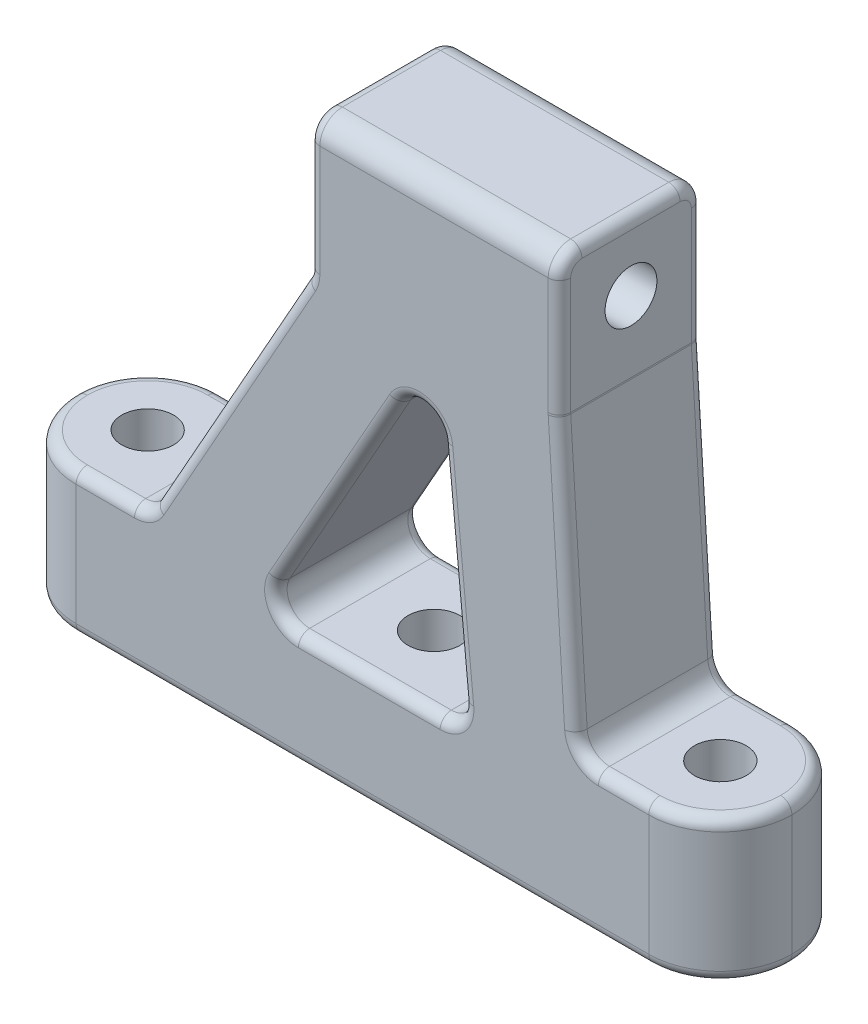
SolidWorks part; units mm, degrees
ref_plane "Front Plane" through (0, 0, 0) normal (0, 0, 1) x (1, 0, 0)
ref_plane "Top Plane" through (0, 0, 0) normal (0, 1, 0) x (1, 0, 0)
ref_plane "Right Plane" through (0, 0, 0) normal (1, 0, 0) x (0, 0, -1)
sketch "Sketch1" plane through (0, 0, 0) normal (0, 0, 1) x (1, 0, 0)
  line L0 (31.75, 0) -> (-31.75, 0)
  line L1 (-31.75, 0) -> (-31.75, 12.7)
  line L2 (-31.75, 12.7) -> (-19.05, 12.7)
  line L3 (-19.05, 12.7) -> (-4.7752, 38.1)
  line L5 (17.4752, 38.1) -> (19.05, 12.7)
  line L6 (19.05, 12.7) -> (31.75, 12.7)
  line L7 (31.75, 12.7) -> (31.75, 0)
  line L8 (-4.7752, 38.1) -> (17.4752, 38.1)
  line L9 (-9.0964, 10) -> (6.4012, 37.5758)
  line L10 (-4.7752, 38.1) -> (17.4752, 38.1)
  line L11 (-4.7752, 38.1) -> (-4.7752, 50.4952)
  line L12 (-4.7752, 50.4952) -> (17.4752, 50.4952)
  line L13 (17.4752, 38.1) -> (17.4752, 50.4952)
  line L14 (6.4012, 37.5758) -> (9.0964, 10)
  line L15 (9.0964, 10) -> (-9.0964, 10)
  line L16 (25.4, 12.7) -> (25.4, 0) construction
  point P4 (0, 0)
  point P14 (6.35, 38.1)
  point P15 (6.35, 50.4952)
  point P17 (0, 10)
  dimension "D1" = 63.5
  dimension "D2" = 12.7
  dimension "D3" = 38.1
  dimension "D4" = 22.2504
  dimension "D5" = 12.3952
  dimension "D6" = 38.1
  dimension "D7" = 10
  dimension "D8" = 10
  dimension "D9" = 19.05
extrude "Boss-Extrude1" add sketch "Sketch1" along normal blind 12.7 contours L16 L6 L5 L8 L3 L2 L1 L0 L14 L15 L9 | L6 L16 L0 L7 | L8 L13 L12 L11 region at (28.575, 6.35, 0) region at (-3.175, 0.6869, 0) region at (6.35, 44.2976, 0)
sketch "Sketch2" plane through (0, 12.7, 0) normal (0, 1, 0) x (1, 0, 0)
  line L0 (-31.75, 0) -> (-19.05, 0) construction
  line L1 (-31.75, -12.7) -> (-31.75, 0) construction
  line L2 (31.75, -12.7) -> (31.75, 0) construction
  circle A0 centre (-25.4, -6.35) radius 2.3
  circle A1 centre (25.4, -6.35) radius 2.3
  circle A2 centre (0, -6.35) radius 2.3
  point P8 (0, 0)
  point P13 (0, 0)
  dimension "D4" = 4.6
  dimension "D1" = 6.35
  dimension "D2" = 6.35
  dimension "D3" = 6.35
extrude "Cut-Extrude1" cut sketch "Sketch2" against normal up to next
sketch "Sketch3" plane through (-4.7752, 0, 0) normal (-1, 0, 0) x (0, 0, 1)
  line L0 (12.7, 38.1) -> (0, 38.1) construction
  line L1 (0, 38.1) -> (0, 50.4952) construction
  circle A0 centre (6.35, 44.45) radius 2.3
  dimension "D1" = 4.6
  dimension "D2" = 6.35
  dimension "D3" = 6.35
extrude "Cut-Extrude2" cut sketch "Sketch3" against normal up to next
fillet "Fillet1" radius 6.35 4 edges at (31.75, 6.35, 0) (31.75, 6.35, 12.7) (-31.75, 6.35, 0) (-31.75, 6.35, 12.7)
fillet "Fillet2" radius 2 9 edges at (6.35, 50.4952, 0) (6.35, 50.4952, 12.7) (9.0964, 10, 6.35) (-9.0964, 10, 6.35) (19.05, 12.7, 6.35) (-19.05, 12.7, 6.35) (-4.7752, 38.1, 6.35) (6.4012, 37.5758, 6.35) (17.4752, 38.1, 6.35)
fillet "Fillet3" radius 1 48 edges at (-7.4044, 10.99, 0) (0.6066, 10, 0) (8.3728, 10.6563, 0) (7.9508, 21.7207, 0) (5.4409, 33.0096, 0) (29.8901, 0, 1.8599) (0, 0, 0) (-29.8901, 0, 1.8599) (-29.8901, 0, 10.8401) (0, 0, 12.7) (-4.8404, 38.1171, 12.7) (-11.7542, 25.6819, 12.7) (-19.2102, 12.9738, 12.7) (-22.8101, 12.7, 12.7) (-29.8901, 12.7, 10.8401) (-29.8901, 12.7, 1.8599) (-22.8101, 12.7, 0) (-19.2102, 12.9738, 0) (-11.7542, 25.6819, 0) (-4.8404, 38.1171, 0) (-4.7752, 43.5593, 0) (-4.7752, 49.9094, 0.5858) (-4.7752, 50.4952, 6.35) (-4.7752, 49.9094, 12.1142) (5.4409, 33.0096, 12.7) (-2.068, 22.5061, 12.7) (-7.4044, 10.99, 12.7) (0.6066, 10, 12.7) (8.3728, 10.6563, 12.7) (17.4762, 38.1, 12.7) (17.4752, 43.3286, 12.7) (17.4752, 49.9094, 12.1142) (17.4752, 50.4952, 6.35) (17.4752, 49.9094, 0.5858) (17.4752, 43.3286, 0) (17.4762, 38.1, 0) (18.2064, 26.3072, 0) (19.5601, 13.2427, 0) (23.1649, 12.7, 0) (29.8901, 12.7, 1.8599) (29.8901, 12.7, 10.8401) (23.1649, 12.7, 12.7) (19.5601, 13.2427, 12.7) (-2.068, 22.5061, 0) (29.8901, 0, 10.8401) (-4.7752, 43.5593, 12.7) (7.9508, 21.7207, 12.7) (18.2064, 26.3072, 12.7)
